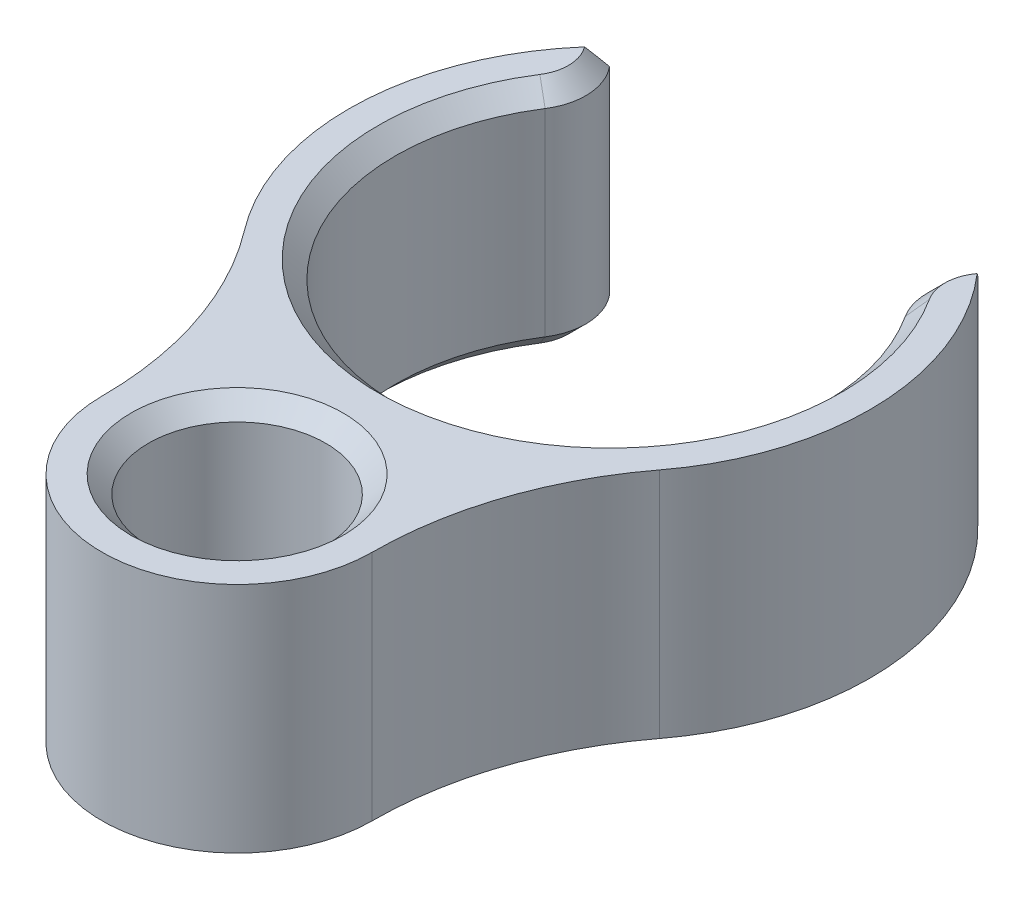
SolidWorks part; units mm, degrees
ref_plane "Front Plane" through (0, 0, 0) normal (0, 0, 1) x (1, 0, 0)
ref_plane "Top Plane" through (0, 0, 0) normal (0, 1, 0) x (1, 0, 0)
ref_plane "Right Plane" through (0, 0, 0) normal (1, 0, 0) x (0, 0, -1)
sketch "Sketch1" plane through (0, 0, 0) normal (0, 1, 0) x (1, 0, 0)
  line L0 (-10.6488, 22.5154) -> (49989.3512, 22.5154) construction
  line L1 (-7.5922, 3.81) -> (49992.4078, 3.81) construction
  line L2 (-6.5054, 22.5154) -> (-7.9196, 23.9296)
  line L3 (6.5054, 22.5154) -> (7.9196, 23.9296)
  line L4 (-6.5054, 22.5154) -> (0, 16.01) construction
  line L5 (0, 16.01) -> (6.5054, 22.5154) construction
  line L6 (-11.2051, 4.81) -> (49988.7949, 4.81) construction
  circle A0 centre (0, 0) radius 3.81
  arc A1 (-5.81, 0) -> (5.81, 0) centre (0, 0) ccw
  arc A2 (-6.5054, 22.5154) -> (6.5054, 22.5154) centre (0, 16.01) ccw
  arc A3 (-7.9196, 23.9296) -> (7.9196, 23.9296) centre (0, 16.01) ccw
  arc A4 (-5.81, 0) -> (-8.9196, 9.2364) centre (-21.0824, 0) ccw
  arc A5 (5.81, 0) -> (8.9196, 9.2364) centre (21.0824, 0) cw
  dimension "D1" = 2
  dimension "D2" = 7.62
  dimension "D3" = 2
  dimension "D4" = 9.2
  dimension "D5" = 1
  dimension "D6" = 90
extrude "Boss-Extrude1" add sketch "Sketch1" along normal blind 10 contours L2 A3 L3 A2 | A1 A5 A3 A4 A0 region at (0, 0, -6.5155) region at (0, 0, -4.5766)
chamfer "Chamfer1" distance 0.75 angle 45 2 edges at (0, 0, 3.81) (0, 10, 3.81)
fillet "Fillet1" radius 2.5 2 edges at (6.5054, 5, -22.5154) (-6.5054, 5, -22.5154)
chamfer "Chamfer2" distance 0.75 angle 45 6 edges at (-7.3485, 0, -22.4853) (7.3485, 0, -22.4853) (0, 0, -6.81) (-7.3485, 10, -22.4853) (7.3485, 10, -22.4853) (0, 10, -6.81)
